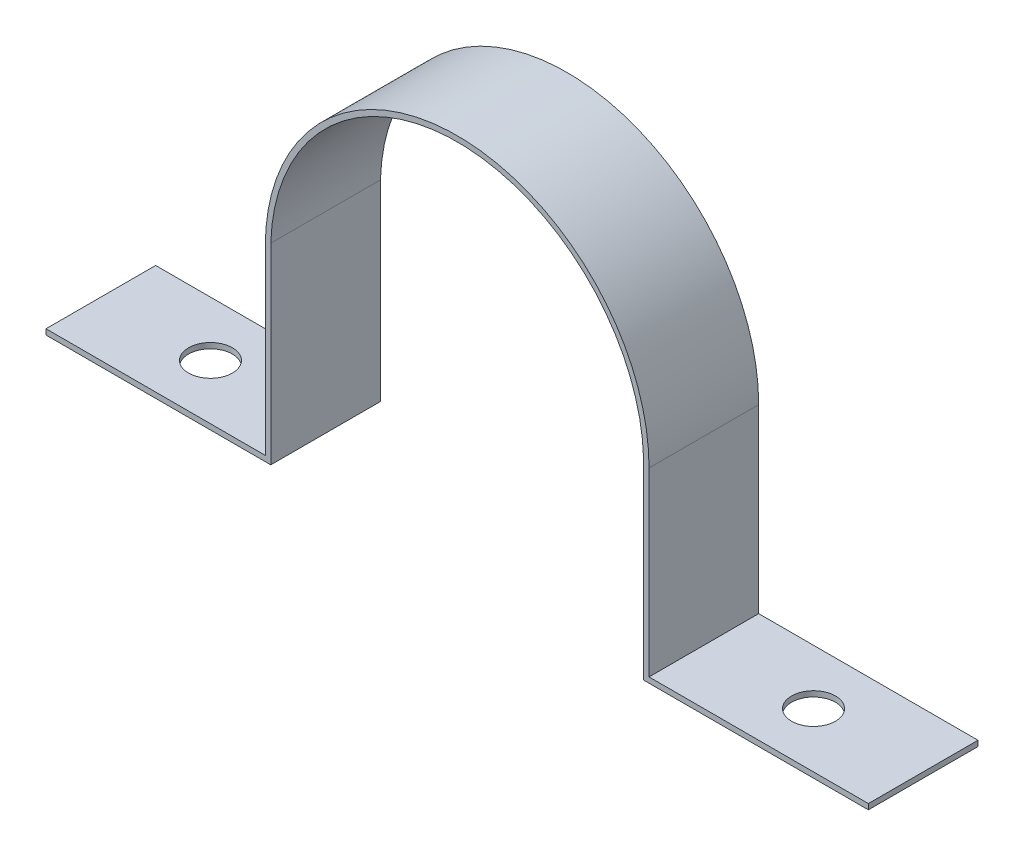
SolidWorks part; units mm, degrees
ref_plane "Alzado" through (0, 0, 0) normal (0, 0, 1) x (1, 0, 0)
ref_plane "Planta" through (0, 0, 0) normal (0, 1, 0) x (1, 0, 0)
ref_plane "Vista lateral" through (0, 0, 0) normal (1, 0, 0) x (0, 0, -1)
sketch "Croquis1" plane through (0, 0, 0) normal (0, 0, 1) x (1, 0, 0)
  line L7 (0, 0) -> (0, -10.2182) construction
  line L12 (-17.5, 0) -> (-17.5, -16.5074)
  line L14 (17, 0.5) -> (17, -17.0074)
  line L16 (-17, 0.5) -> (-17, -17.0074)
  line L17 (17, 17.0074) -> (-17, -17.0074) construction
  line L18 (17, -17.0074) -> (-17, 17.0074) construction
  line L20 (17.5, 0) -> (17.5, -16.5074)
  line L22 (-17, -17.0074) -> (-37.5, -17.0074)
  line L23 (-37.5, -17.0074) -> (-37.5, -16.5074)
  line L24 (-37.5, -16.5074) -> (-17.5, -16.5074)
  line L25 (-17.5, 17.5074) -> (-17.5, -17.5074) construction
  line L26 (17.5, -17.5074) -> (-17.5, -17.5074) construction
  line L27 (37.5, -16.5074) -> (17.5, -16.5074)
  line L28 (37.5, -17.0074) -> (37.5, -16.5074)
  line L29 (17, -17.0074) -> (37.5, -17.0074)
  line L30 (17.5, 17.5074) -> (17.5, -17.5074) construction
  line L31 (17, -17.0074) -> (-17, -17.0074) construction
  line L32 (17.5, 17.5074) -> (-17.5, 17.5074) construction
  line L33 (17, 17.0074) -> (-17, 17.0074) construction
  line L34 (-17, 17.0074) -> (-17, -17.0074) construction
  line L35 (17, 17.0074) -> (17, -17.0074) construction
  arc A1 (17.5, 0) -> (-17.5, 0) centre (0, 0) ccw
  arc A4 (17, 0.5) -> (-17, 0.5) centre (0, 0) ccw
  dimension "D1" = 17.5
  dimension "D2" = 0.5
  dimension "D6" = 17.0074
  dimension "D3" = 20
  dimension "D5" = 17.5074
extrude "Saliente-Extruir1" add sketch "Croquis1" along normal blind 10
sketch "Croquis2" plane through (0, -16.5074, 0) normal (0, 1, 0) x (1, 0, 0)
  line L0 (-17.5, -10) -> (-17.5, 0) construction
  line L1 (17.5, -10) -> (17.5, 0) construction
  line L2 (-37.5, -10) -> (-37.5, 0) construction
  circle A0 centre (-27.5, -5) radius 2
  circle A1 centre (27.5, -5) radius 2
  point P10 (-37.5, -5)
  point P11 (0, 0)
  dimension "D1" = 10
  dimension "D3" = 4
  dimension "D2" = 10
extrude "Cortar-Extruir1" cut sketch "Croquis2" against normal blind 10
